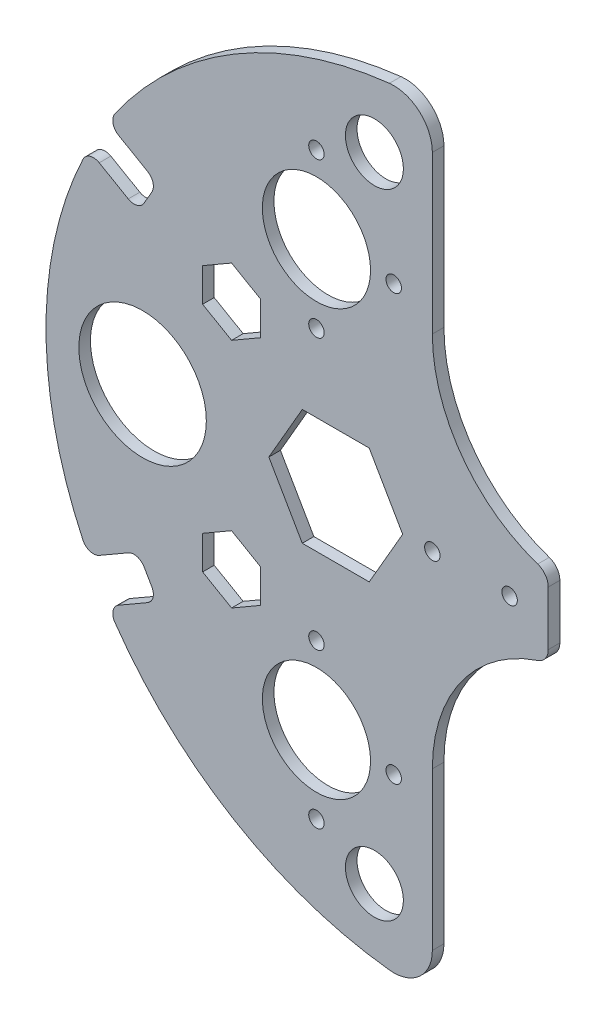
SolidWorks part; units mm, degrees
ref_plane "前视基准面" through (0, 0, 0) normal (0, 0, 1) x (1, 0, 0)
ref_plane "上视基准面" through (0, 0, 0) normal (0, 1, 0) x (1, 0, 0)
ref_plane "右视基准面" through (0, 0, 0) normal (1, 0, 0) x (0, 0, -1)
other "Configuration Table"
sketch "草图2" plane through (0, 0, 0) normal (0, 0, 1) x (1, 0, 0)
  line L0 (0, 100) -> (0, 10)
  line L1 (0, -10) -> (30, -10)
  line L2 (0, -10) -> (0, 10)
  line L3 (0, 10) -> (30, 10)
  line L4 (30, -10) -> (30, 10)
  line L5 (0, -100) -> (0, -10)
  line L6 (-196.1637, 0) -> (147.6162, 0) construction
  arc A0 (0, -100) -> (0, 100) centre (0, 0) cw
  circle A1 centre (-30, 55) radius 14
  circle A3 centre (-75, 0) radius 16.5
  circle A4 centre (-30, -55) radius 14
  circle A5 centre (-30, 55) radius 20 construction
  circle A6 centre (-10, 55) radius 2
  circle A7 centre (-30, 75) radius 2
  circle A8 centre (-30, 35) radius 2
  circle A9 centre (-30, -35) radius 2
  circle A10 centre (-10, -55) radius 2
  circle A11 centre (-30, -75) radius 2
  dimension "D3" = 100
  dimension "D4" = 28
  dimension "D5" = 40
  dimension "D6" = 33
  dimension "D7" = 75
  dimension "D8" = 55
  dimension "D9" = 30
  dimension "D10" = 4
  dimension "D11" = 4
  dimension "D12" = 4
  dimension "D1" = 20
  dimension "D2" = 30
extrude "凸台-拉伸1" add sketch "草图2" along normal blind 3 contours A0 L6 A3 L2 L0 A1 | L6 A0 L5 L2 A3 A4 | L6 L2 L1 L4 | L2 L6 L4 L3 region at (-41.623, 0, 0) region at (15, 0, 0)
fillet "圆角1" radius 40 2 edges at (0, -10, 1.5) (0, 10, 1.5)
fillet "圆角2" radius 10 2 edges at (0, 100, 1.5) (0, -100, 1.5)
sketch "草图3" plane through (0, 0, 3) normal (0, 0, 1) x (1, 0, 0)
  line L0 (-167.0568, 0) -> (151.3553, 0) construction
  line L2 (0, 0) -> (-130.7971, 75.5157) construction
  line L3 (-42.3205, 0) -> (-33.6603, -15)
  line L4 (-33.6603, -15) -> (-16.3397, -15)
  line L5 (-16.3397, -15) -> (-7.6795, 0)
  line L6 (-7.6795, 0) -> (-16.3397, 15)
  line L7 (-16.3397, 15) -> (-33.6603, 15)
  line L8 (-33.6603, 15) -> (-42.3205, 0)
  line L9 (-71.1122, 46.8301) -> (-128.2971, 79.8458)
  line L10 (-76.1122, 38.1699) -> (-133.2971, 71.1856)
  line L11 (-2.5, -4.3301) -> (-133.2971, 71.1856) construction
  line L12 (2.5, 4.3301) -> (-128.2971, 79.8458) construction
  line L13 (-71.1122, 46.8301) -> (-76.1122, 38.1699)
  line L14 (0, 48.7298) -> (0, 89.4427) construction
  line L16 (-59.4615, 34.3301) -> (-59.4615, 25.6699)
  line L17 (-59.4615, 25.6699) -> (-51.9615, 21.3397)
  line L18 (-51.9615, 21.3397) -> (-44.4615, 25.6699)
  line L19 (-44.4615, 25.6699) -> (-44.4615, 34.3301)
  line L20 (-44.4615, 34.3301) -> (-51.9615, 38.6603)
  line L21 (-51.9615, 38.6603) -> (-59.4615, 34.3301)
  circle A0 centre (-25, 0) radius 15 construction
  arc A1 (-11.1111, 99.3808) -> (-11.1111, -99.3808) centre (0, 0) ccw construction
  circle A2 centre (-15, 82) radius 7.5
  circle A3 centre (-51.9615, 30) radius 7.5 construction
  point P30 (-59.4615, 34.3301)
  arc M4 (-11.1111, 99.3808) -> (-11.1111, -99.3808) centre (0, 0) ccw
  dimension "D2" = 30
  dimension "D3" = 25
  dimension "D8" = 15
  dimension "D9" = 82
  dimension "D10" = 15
  dimension "D11" = 15
  dimension "D12" = 60
  dimension "D4" = 30
  dimension "D7" = 85
  dimension "D5" = 5
  dimension "D6" = 5
extrude "切除-拉伸1" cut sketch "草图3" against normal through all contours L13 L9 L10 M4 | L3 L4 L5 L6 L7 L8 | L16 L17 L18 L19 L20 L21 | A2 region at (-80.0893, 46.2396, 3)
fillet "圆角3" radius 3 4 edges at (-71.1122, 46.8301, 1.5) (-76.1122, 38.1699, 1.5) (-88.9942, 45.6073, 1.5) (-83.9942, 54.2676, 1.5)
mirror "镜向1" about plane through (0, 0, 0) normal (0, 1, 0) of "切除-拉伸1", "圆角3"
sketch "草图4" plane through (0, 0, 3) normal (0, 0, 1) x (1, 0, 0)
  line L0 (-26.0841, 0) -> (107.7079, 0) construction
  line L1 (30, -10) -> (30, 10) construction
  circle A0 centre (20, 0) radius 2
  circle A1 centre (0, 0) radius 2
  arc A4 (-18, 0) -> (-22, 0) centre (-20, 0) ccw [skipped]
  dimension "D1" = 4
  dimension "D2" = 10
  dimension "D4" = 20
  dimension "D3" = 3
extrude "切除-拉伸2" cut sketch "草图4" against normal through all
fillet "圆角4" radius 4 2 edges at (30, -10, 1.5) (30, 10, 1.5)
